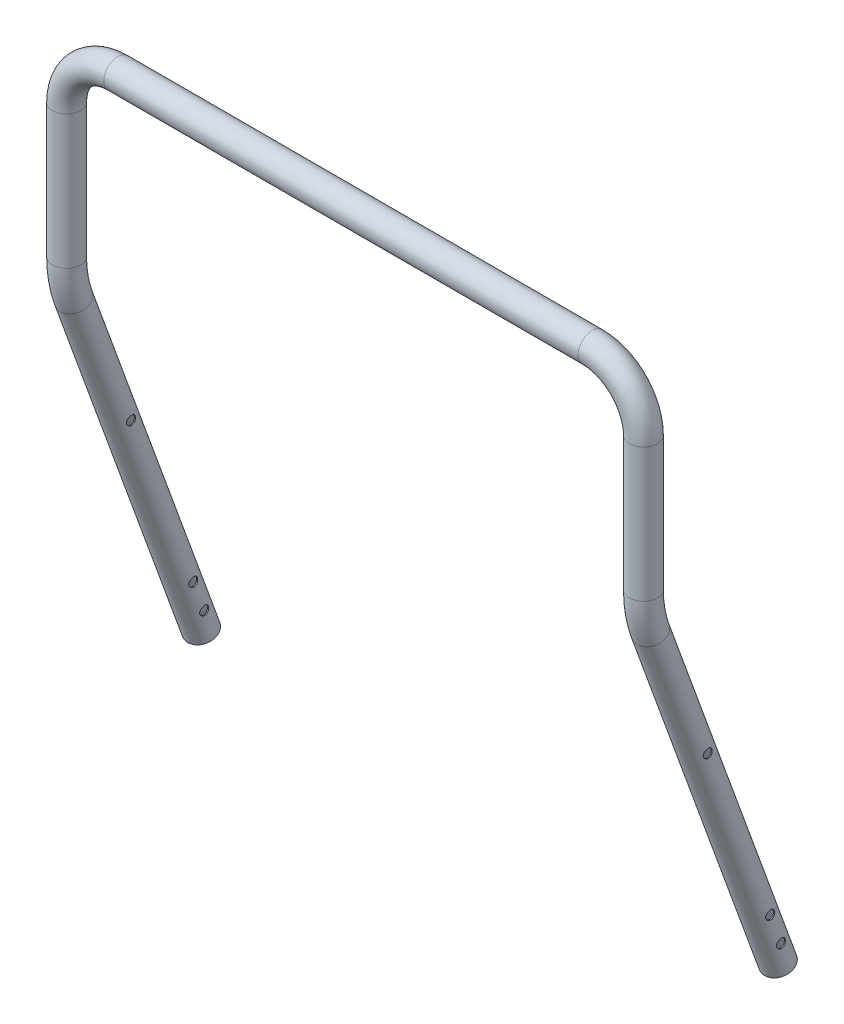
SolidWorks part; units mm, degrees
ref_plane "Front Plane" through (0, 0, 0) normal (0, 0, 1) x (1, 0, 0)
ref_plane "Top Plane" through (0, 0, 0) normal (0, 1, 0) x (1, 0, 0)
ref_plane "Right Plane" through (0, 0, 0) normal (1, 0, 0) x (0, 0, -1)
sketch "Sketch8" plane through (0, 0, 0) normal (0, 0, 1) x (1, 0, 0)
  line L0 (-185, 0) -> (185, 0)
  line L1 (-225, -40) -> (-225, -100)
  line L2 (225, -40) -> (225, -100)
  arc A0 (225, -40) -> (185, 0) centre (185, -40) ccw
  arc A1 (-185, 0) -> (-225, -40) centre (-185, -40) ccw
  point P4 (0, 0)
  point P9 (225, 0)
  point P12 (-225, 0)
  dimension "D2" = 40
  dimension "450" = 450
  dimension "D3" = 60
  dimension "D4" = 60
ref_plane "Plane3" through (225, -100, 0) normal (0, -1, 0) x (-1, 0, 0)
sketch "Sketch9" plane through (225, -100, 0) normal (0, -1, 0) x (-1, 0, 0)
  circle A0 centre (0, 0) radius 11
  circle A1 centre (0, 0) radius 10.2
  dimension "D1" = 0.8
ref_plane "Plane5" through (225, 0, 0) normal (1, 0, 0) x (0, 0, -1)
sketch "Sketch13" plane through (225, 0, 0) normal (1, 0, 0) x (0, 0, -1)
  line L0 (0, -100) -> (0, -144.2597)
  line L1 (-11, -100) -> (11, -100) construction
  line L2 (5.4277, -175.0415) -> (104.9678, -448.5257)
  arc A0 (5.4277, -175.0415) -> (0, -144.2597) centre (90, -144.2597) cw
  dimension "D1" = 90
  dimension "D2" = 160
sweep "Sweep2" add profiles "Sketch9" path "Sketch8"
sweep "Sweep3" add profiles "Sketch9<2>" path "Sketch13"
sketch "Sketch9<2>" plane through (225, -100, 0) normal (0, -1, 0) x (-1, 0, 0) same geometry as "Sketch9"
mirror "Mirror1" about plane through (0, 0, 0) normal (1, 0, 0) of "Sweep3"
sketch "Sketch14" plane through (225, 0, 0) normal (1, 0, 0) x (0, 0, -1)
  line L0 (104.9678, -448.5257) -> (5.4277, -175.0415) construction
  line L1 (94.6311, -452.2879) -> (115.3044, -444.7635) construction
  line L2 (15.7643, -171.2793) -> (-4.909, -178.8037) construction
  circle A0 centre (39.6596, -269.0931) radius 3.5
  circle A1 centre (88.2265, -402.5295) radius 3.5
  circle A3 centre (96.777, -426.0218) radius 3.5
  circle A4 centre (0, 0) radius 10.2 construction
  dimension "D1" = 142
  dimension "D2" = 25
  dimension "D3" = 272
extrude "Cut-Extrude1" cut sketch "Sketch14" against normal up to next and the other way up to next
mirror "Mirror2" about plane through (0, 0, 0) normal (1, 0, 0) of "Cut-Extrude1"
